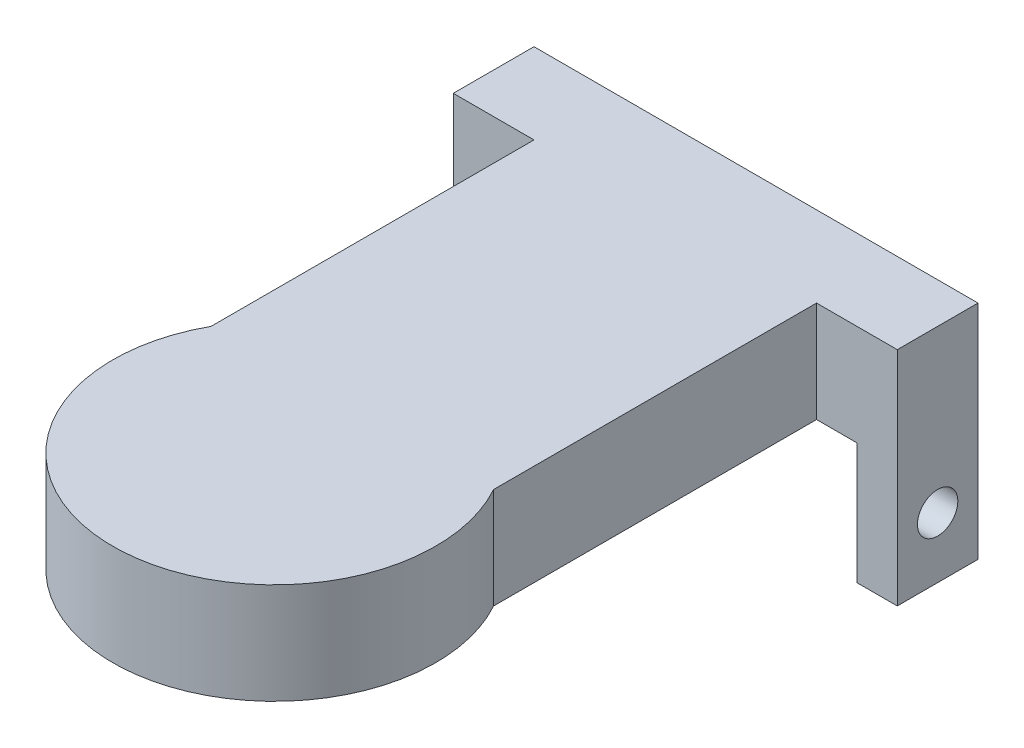
SolidWorks part; units mm, degrees
ref_plane "Front Plane" through (0, 0, 0) normal (0, 0, 1) x (1, 0, 0)
ref_plane "Top Plane" through (0, 0, 0) normal (0, 1, 0) x (1, 0, 0)
ref_plane "Right Plane" through (0, 0, 0) normal (1, 0, 0) x (0, 0, -1)
sketch "Sketch1" plane through (0, 0, 0) normal (0, 1, 0) x (1, 0, 0)
  circle A21 centre (0, 0) radius 20
  dimension "D1" = 40
extrude "Boss-Extrude1" add sketch "Sketch1" along normal blind 10
sketch "Sketch2" plane through (0, 10, 0) normal (0, 1, 0) x (1, 0, 0)
  line L0 (-1, 4.9246) -> (-1, 3.9246)
  line L1 (-1, 4.9246) -> (1, 4.9246)
  line L2 (1, 4.9246) -> (1, 3.9246)
  arc A0 (-1, 3.9246) -> (1, 3.9246) centre (0, 0) ccw
  point P5 (0, 4.9246)
  dimension "D1" = 8.1
  dimension "D2" = 1
  dimension "D3" = 2
extrude "Cut-Extrude1" cut sketch "Sketch2" against normal through all
sketch "Sketch3" plane through (0, 0, 0) normal (0, 1, 0) x (1, 0, 0)
  line L0 (-17.5, 59.6825) -> (-17.5, 9.6825)
  line L1 (-17.5, 59.6825) -> (17.5, 59.6825)
  line L2 (17.5, 59.6825) -> (17.5, 9.6825)
  circle A0 centre (0, 0) radius 20 construction
  arc A1 (17.5, 9.6825) -> (-17.5, 9.6825) centre (0, 0) ccw
  point P6 (0, 59.6825)
  dimension "D1" = 35
  dimension "D2" = 50
extrude "Boss-Extrude2" add sketch "Sketch3" along normal up to surface (10 mm away) up to face at (0, 10, -2.431)
sketch "Sketch5" plane through (0, 0, 0) normal (0, -1, 0) x (1, 0, 0)
  line L0 (-1, -3.9246) -> (-1, -4.9246)
  line L1 (-1, -4.9246) -> (1, -4.9246)
  line L2 (1, -4.9246) -> (1, -3.9246)
  circle A0 centre (0, 0) radius 12.5
  arc A1 (1, -3.9246) -> (-1, -3.9246) centre (0, 0) ccw
  dimension "D1" = 25
extrude "Boss-Extrude3" add sketch "Sketch5" along normal blind 6
sketch "Sketch6" plane through (0, 0, -59.6825) normal (0, 0, -1) x (-1, 0, 0)
  line L0 (-27.5, 10) -> (27.5, 10)
  line L1 (-27.5, 10) -> (-27.5, -15)
  line L2 (-27.5, -15) -> (-22.5, -15)
  line L3 (-22.5, -15) -> (-22.5, 0)
  line L4 (-22.5, 0) -> (22.5, 0)
  line L5 (22.5, 0) -> (22.5, -15)
  line L6 (22.5, -15) -> (27.5, -15)
  line L7 (27.5, -15) -> (27.5, 10)
  line L8 (-17.5, 10) -> (17.5, 10) construction
  line L9 (-17.5, 0) -> (17.5, 0) construction
  point P10 (0, 0)
  dimension "D1" = 45
  dimension "D2" = 5
  dimension "D3" = 15
extrude "Boss-Extrude4" add sketch "Sketch6" against normal blind 10
sketch "Sketch7" plane through (27.5, 0, 0) normal (1, 0, 0) x (0, 0, -1)
  line L0 (49.6825, -15) -> (59.6825, -15) construction
  line L1 (9.6825, 0) -> (49.6825, 0) construction
  circle A0 centre (54.6825, -7.5) radius 2.5
  point P4 (54.6825, -15)
  dimension "D2" = 5
  dimension "D1" = 7.5
extrude "Cut-Extrude2" cut sketch "Sketch7" against normal through all
sketch "Sketch8" plane through (0, 10, 0) normal (0, 1, 0) x (1, 0, 0)
  line L0 (-27.5, 49.6825) -> (-27.5, 59.6825) construction
  line L1 (-27.5, 59.6825) -> (27.5, 59.6825)
  line L2 (-27.5, 59.6825) -> (-27.5, 49.6825)
  line L3 (-27.5, 49.6825) -> (-17.5, 49.6825)
  line L4 (27.5, 59.6825) -> (27.5, 49.6825)
  line L5 (27.5, 59.6825) -> (-27.5, 59.6825) construction
  line L6 (17.5, 49.6825) -> (27.5, 49.6825)
  line L8 (-17.5, 49.6825) -> (-17.5, 9.6825)
  line L10 (17.5, 49.6825) -> (17.5, 9.6825)
  arc A0 (-17.5, 9.6825) -> (17.5, 9.6825) centre (0, 0) ccw
extrude "Boss-Extrude5" add sketch "Sketch8" along normal blind 2.5
sketch "Sketch9" plane through (0, -6, 0) normal (0, -1, 0) x (1, 0, 0)
  circle A0 centre (0, 0) radius 12.5
  circle A1 centre (0, 0) radius 12.5 construction
extrude "Cut-Extrude3" cut sketch "Sketch9" against normal blind 2.5
